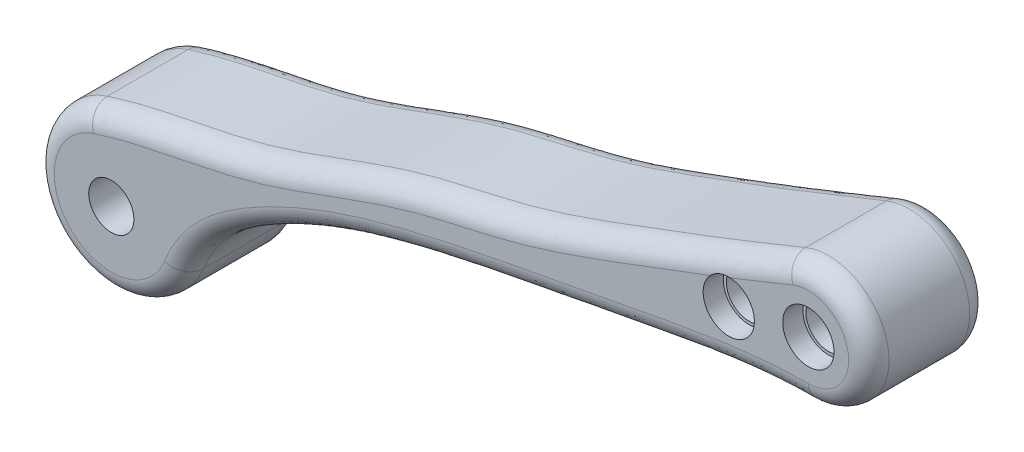
SolidWorks part; units mm, degrees
ref_plane "Alzado" through (0, 0, 0) normal (0, 0, 1) x (1, 0, 0)
ref_plane "Planta" through (0, 0, 0) normal (0, 1, 0) x (1, 0, 0)
ref_plane "Vista lateral" through (0, 0, 0) normal (1, 0, 0) x (0, 0, -1)
sketch "Croquis2" plane through (0, 0, 0) normal (0, 0, 1) x (1, 0, 0)
  line L0 (85.8255, 85.7198) -> (57.4651, 82.7953) construction
  line L1 (57.4651, 82.7953) -> (-17.2776, 54.2727) construction
  line L2 (57.4651, 82.7953) -> (56.3004, 88.6812) construction
  line L5 (57.4651, 82.7953) -> (59.018, 74.9475) construction
  line L6 (56.3004, 88.6812) -> (59.018, 74.9475) construction
  line L7 (20.0938, 68.534) -> (17.4198, 75.5412) construction
  line L8 (20.0938, 68.534) -> (22.7677, 61.5269) construction
  line L9 (-17.2776, 54.2727) -> (-31.2918, 48.9248) construction
  line L11 (151.8102, 120.4654) -> (157.4651, 106.5722) construction
  line L12 (137.745, 103.2377) -> (157.4651, 106.5722) construction
  line L13 (157.4651, 106.5722) -> (157.4651, 91.5722) construction
  line L14 (165.556, 93.9414) -> (85.8255, 85.7198) construction
  line L16 (-12.7549, 42.4211) -> (-7.6244, 30.706) construction
  line L17 (85.8255, 85.7198) -> (86.3384, 80.7462) construction
  line L19 (108.1255, 88.0193) -> (106.5869, 102.9402) construction
  line L20 (85.8255, 85.7198) -> (84.7998, 95.667) construction
  line L21 (170.4761, 99.1081) -> (108.1255, 88.0193) construction
  line L22 (-17.2776, 54.2727) -> (-12.7549, 42.4211) construction
  line L23 (-17.2776, 54.2727) -> (-21.2561, 66.4275) construction
  line L24 (119.2548, 89.9986) -> (119.7801, 87.045) construction
  line L25 (-15.3022, 48.2378) -> (2.5237, 41.27) construction
  arc A2 (157.4651, 91.5722) -> (151.8102, 120.4654) centre (157.4651, 106.5722) ccw
  circle A5 centre (137.745, 103.2377) radius 6.35
  circle A9 centre (157.4651, 106.5722) radius 6.35
  circle A13 centre (-15.3022, 48.2378) radius 6.35
  arc A15 (-21.2561, 66.4275) -> (2.5237, 41.27) centre (-15.3022, 48.2378) ccw
  spline S0 degree 3 poles (151.8102, 120.4654) (134.4317, 113.392) (115.1459, 105.9714) (82.8284, 94.3392) (52.2361, 89.0511) (18.2273, 73.5187) (-8.2853, 70.6731) (-21.2561, 66.4275) knots 0 0 0 0 0.267089 0.393579 0.55517 0.781181 1 1 1 1
  spline S1 degree 3 poles (2.5237, 41.27) (6.2703, 50.8551) (25.1058, 64.9093) (55.3958, 74.7142) (88.3439, 81.1686) (121.0022, 87.3319) (144.8055, 91.5722) (157.4651, 91.5722) knots 0 0 0 0 0.171275 0.402453 0.569484 0.773002 1 1 1 1
  dimension "D2" = 10
  dimension "D15" = 12.7
  dimension "D16" = 3
  dimension "D18" = 12.7
  dimension "D19" = 5
  dimension "D11" = 12.7
  dimension "D4" = 195
  dimension "D7" = 80
  dimension "D9" = 15
  dimension "D6" = 15
  dimension "D17" = 45
  dimension "D3" = 100
  dimension "D14" = 15
  dimension "D5" = 20
  dimension "D8" = 8
  dimension "D10" = 6
  dimension "D12" = 7.5
  dimension "D13" = 7.5
extrude "Saliente-Extruir1" add sketch "Croquis2" along normal blind 30
ref_plane "Plano1" through (0, 0, 30) normal (0, 0, 1) x (1, 0, 0)
sketch "Croquis5" plane through (0, 0, 0) normal (0, 0, -1) x (-1, 0, 0)
  circle A0 centre (-157.4651, 106.5722) radius 2.5
  circle A1 centre (-157.4651, 106.5722) radius 7.4433
  circle A2 centre (-137.745, 103.2377) radius 2.5
  circle A3 centre (-137.745, 103.2377) radius 7.335
extrude "Saliente-Extruir4" add sketch "Croquis5" against normal blind 30
sketch "Croquis6" plane through (0, 0, 0) normal (0, 0, -1) x (-1, 0, 0)
  circle A0 centre (-137.745, 103.2377) radius 6.35
  circle A1 centre (-137.745, 103.2377) radius 2.5
extrude "Cortar-Extruir2" cut sketch "Croquis6" against normal blind 5 contours A0
sketch "Croquis7" plane through (0, 0, 5) normal (0, 0, -1) x (-1, 0, 0)
  circle A0 centre (-137.745, 103.2377) radius 5.6
  dimension "D1" = 11.2
extrude "Cortar-Extruir3" cut sketch "Croquis7" against normal blind 30 contours A0
sketch "Croquis8" plane through (0, 0, 30) normal (0, 0, 1) x (1, 0, 0)
  circle A0 centre (137.745, 103.2377) radius 6.35
  circle A1 centre (137.745, 103.2377) radius 5.6
  dimension "D1" = 12.7
  dimension "D2" = 11.2
extrude "Cortar-Extruir4" cut sketch "Croquis8" against normal blind 5
sketch "Croquis9" plane through (0, 0, 0) normal (0, 0, -1) x (-1, 0, 0)
  circle A1 centre (-157.4651, 106.5722) radius 5.6
  circle A3 centre (-137.745, 103.2377) radius 5.6 construction
extrude "Cortar-Extruir6" cut sketch "Croquis9" against normal blind 30
sketch "Croquis10" plane through (0, 0, 0) normal (0, 0, -1) x (-1, 0, 0)
  circle A0 centre (-157.4651, 106.5722) radius 6.35
  circle A1 centre (-137.745, 103.2377) radius 6.35 construction
extrude "Cortar-Extruir7" cut sketch "Croquis10" against normal blind 5
sketch "Croquis11" plane through (0, 0, 30) normal (0, 0, 1) x (1, 0, 0)
  circle A0 centre (157.4651, 106.5722) radius 6.35
  circle A2 centre (137.745, 103.2377) radius 6.35 construction
extrude "Cortar-Extruir8" cut sketch "Croquis11" against normal blind 5
sketch "Croquis14" plane through (0, 0, 0) normal (0, 0, -1) x (-1, 0, 0)
  circle A0 centre (15.3022, 48.2378) radius 6.35
  circle A1 centre (15.3022, 48.2378) radius 5.6
  dimension "D1" = 11.2
extrude "Saliente-Extruir5" add sketch "Croquis14" against normal blind 30
sketch "Croquis15" plane through (0, 0, 0) normal (0, 0, -1) x (-1, 0, 0)
  circle A1 centre (15.3022, 48.2378) radius 6.35
  dimension "D1" = 12.7
sketch "Croquis16" plane through (0, 0, 30) normal (0, 0, 1) x (1, 0, 0)
  circle A0 centre (-15.3022, 48.2378) radius 6.35
  dimension "D1" = 12.7
fillet "Redondeo1" radius 5 4 edges at (172.1858, 109.4533, 30) (-29.2112, 35.0905, 30)
fillet "Redondeo2" radius 5 4 edges at (172.1858, 109.4533, 0) (-29.2112, 35.0905, 0)
